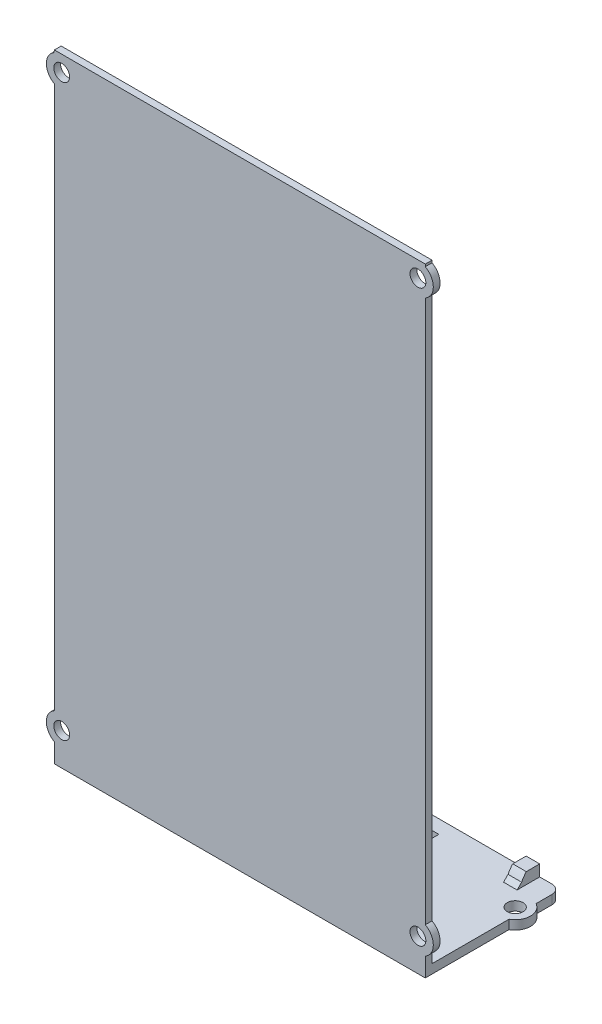
SolidWorks part; units mm, degrees
ref_plane "Front Plane" through (0, 0, 0) normal (0, 0, 1) x (1, 0, 0)
ref_plane "Top Plane" through (0, 0, 0) normal (0, 1, 0) x (1, 0, 0)
ref_plane "Right Plane" through (0, 0, 0) normal (1, 0, 0) x (0, 0, -1)
sketch "Sketch1" plane through (0, 0, 0) normal (0, 0, 1) x (1, 0, 0)
  line L0 (-37.75, -134.5) -> (37.75, -134.5)
  line L1 (-41, -126.5135) -> (-41, -6.4865) construction
  line L2 (-37.75, -132.4865) -> (-37.75, -134.5) construction
  line L3 (41, 0) -> (-41, 0) construction
  line L4 (41, -0.5135) -> (41, 0) construction
  line L5 (-37.75, -7) -> (-37.75, -126.5135) construction
  line L6 (37.75, -7) -> (-37.75, -7) construction
  line L28 (-41, -6.4865) -> (-41, -126.5135)
  line L29 (-41, -132.4865) -> (-41, -134.5)
  line L30 (-41, -134.5) -> (-37.75, -134.5)
  line L31 (-37.75, -134.5) -> (-37.75, -132.4865) construction
  line L32 (-37.75, -126.5135) -> (-37.75, -7) construction
  line L33 (-37.75, -7) -> (37.75, -7) construction
  line L34 (37.75, -7) -> (37.75, -126.5135) construction
  line L35 (37.75, -132.4865) -> (37.75, -134.5) construction
  line L36 (37.75, -134.5) -> (41, -134.5)
  line L37 (41, -134.5) -> (41, -132.4865)
  line L38 (41, -126.5135) -> (41, -6.4865)
  line L39 (41, -0.5135) -> (41, 0)
  line L40 (41, 0) -> (-41, 0)
  line L41 (-41, 0) -> (-41.0728, -0.5543)
  circle A0 centre (-39.375, -129.5) radius 1.75
  circle A1 centre (39.375, -129.5) radius 1.75
  circle A2 centre (39.375, -3.5) radius 1.75
  circle A3 centre (-39.375, -3.5) radius 1.75
  arc A4 (-37.75, -132.4865) -> (-37.75, -126.5135) centre (-39.375, -129.5) ccw construction
  arc A5 (41, -6.4865) -> (41, -0.5135) centre (39.375, -3.5) ccw construction
  arc A12 (-41, -126.5135) -> (-41, -132.4865) centre (-39.375, -129.5) ccw
  arc A13 (-37.75, -132.4865) -> (-37.75, -126.5135) centre (-39.375, -129.5) ccw construction
  arc A14 (37.75, -126.5135) -> (37.75, -132.4865) centre (39.375, -129.5) ccw construction
  arc A15 (41, -132.4865) -> (41, -126.5135) centre (39.375, -129.5) ccw
  arc A16 (41, -6.4865) -> (41, -0.5135) centre (39.375, -3.5) ccw
  arc A17 (-41.0728, -0.5543) -> (-41, -6.4865) centre (-39.375, -3.5) ccw
  dimension "D2" = 3.5
extrude "Boss-Extrude1" add sketch "Sketch1" along normal blind 1.5
sketch "Sketch2" plane through (-41, 0, 0) normal (-1, 0, 0) x (0, 0, 1)
  line L0 (1.5, -134.5) -> (1.5, -136.7)
  line L1 (1.5, -136.7) -> (-40, -136.7)
  line L2 (-40, -136.7) -> (-40, -134.7)
  line L3 (-40, -134.7) -> (0, -134.7)
  line L4 (0, -134.7) -> (0, -134.5)
  line L10 (0, -132.4865) -> (0, -134.5)
  line L11 (0, -134.5) -> (1.5, -134.5)
  line L12 (1.5, -134.5) -> (1.5, -132.4865)
  line L13 (1.5, -132.4865) -> (0, -132.4865)
  line L14 (0, -132.4865) -> (0, -134.5)
  line L16 (1.5, -134.5) -> (1.5, -132.4865)
  line L17 (1.5, -132.4865) -> (0, -132.4865)
  dimension "D1" = 2
  dimension "D2" = 0.2
  dimension "D4" = 40
  dimension "D3" = 0
extrude "Boss-Extrude2" add sketch "Sketch2" against normal up to surface (82 mm away) up to face at (41, -133.4933, 0.75)
sketch "Sketch3" plane through (-15, 0, 0) normal (1, 0, 0) x (0, 0, -1)
  line L0 (0, -119.7) -> (15, -134.7)
  line L1 (0, -126.5135) -> (0, -6.4865) construction
  line L2 (40, -134.7) -> (0, -134.7) construction
  line L3 (15, -134.7) -> (0, -134.7)
  line L4 (0, -134.7) -> (0, -119.7)
  dimension "D1" = 15
extrude "Boss-Extrude3" add sketch "Sketch3" along normal blind 1.5 and the other way blind 1.5
sketch "Sketch4" plane through (0, -136.7, 0) normal (0, -1, 0) x (1, 0, 0)
  line L0 (-41, -17.0135) -> (-41, -22.9865)
  line L1 (41, -17.0135) -> (41, -22.9865)
  line L9 (-41, -40) -> (-41, 1.5) construction
  line L10 (41, 1.5) -> (41, -40) construction
  line L11 (41, -17.0135) -> (39.375, -20) construction
  line L12 (39.375, -20) -> (41, -22.9865) construction
  arc A2 (-41, -17.0135) -> (-41, -22.9865) centre (-39.375, -20) ccw
  arc A3 (41, -22.9865) -> (41, -17.0135) centre (39.375, -20) ccw
  arc A4 (-41, -17.0135) -> (-41, -22.9865) centre (-39.375, -20) ccw construction
  arc A5 (41, -22.9865) -> (41, -17.0135) centre (39.375, -20) ccw construction
extrude "Boss-Extrude4" add sketch "Sketch4" against normal blind 2
sketch "Sketch5" plane through (0, -136.7, 0) normal (0, -1, 0) x (1, 0, 0)
  arc A0 (41, -22.9865) -> (41, -17.0135) centre (39.375, -20) ccw construction
  circle A1 centre (39.375, -20) radius 1.75
  circle A6 centre (-39.375, -20) radius 1.75
  arc A7 (-41, -17.0135) -> (-41, -22.9865) centre (-39.375, -20) ccw construction
  dimension "D1" = 3.5
  dimension "D2" = 3.5
extrude "Cut-Extrude1" cut sketch "Sketch5" against normal blind 2
sketch "Sketch6" plane through (0, -136.7, 0) normal (0, -1, 0) x (1, 0, 0)
  line L0 (-57.6714, -28.5) -> (65.3337, -28.5)
extrude "Cut-Extrude2" cut sketch "Sketch6" against normal through all and the other way through all
sketch "Sketch7" plane through (0, -136.7, 0) normal (0, -1, 0) x (1, 0, 0)
  line L0 (-41, -28.5) -> (41, -28.5) construction
  line L1 (-36.3, -28.5) -> (-33.3, -28.5)
  line L2 (-36.3, -28.5) -> (-36.3, -24.5)
  line L3 (-36.3, -24.5) -> (-33.3, -24.5)
  line L4 (-33.3, -28.5) -> (-33.3, -24.5)
  line L5 (-41, -25.7433) -> (-36.3, -25.7433) construction
  line L6 (36.3, -28.5) -> (33.3, -28.5)
  line L7 (36.3, -28.5) -> (36.3, -24.5)
  line L8 (36.3, -24.5) -> (33.3, -24.5)
  line L9 (33.3, -28.5) -> (33.3, -24.5)
  line L10 (-41, -28.5) -> (-41, -22.9865) construction
  line L11 (36.3, -24.5) -> (41, -24.5) construction
  line L12 (41, -22.9865) -> (41, -28.5) construction
  dimension "D1" = 4.7
  dimension "D2" = 3
  dimension "D3" = 4
extrude "Boss-Extrude6" add sketch "Sketch7" against normal blind 2.5 from surface at -2 starting at face at (-39.375, -134.7, -21.75)
fillet "Fillet1" radius 2 2 edges at (-41, -135.7, -28.5) (41, -135.7, -28.5)
chamfer "Chamfer1" distance 1 angle 45 4 edges at (-34.8, -132.2, -24.5) (34.8, -132.2, -24.5) (-34.8, -134.7, -24.5) (34.8, -134.7, -24.5)
fillet "Fillet2" radius 8 2 edges at (-34.8, -133.2, -24.5) (34.8, -133.2, -24.5)
sketch "Sketch8" plane through (0, -136.7, 0) normal (0, -1, 0) x (1, 0, 0)
  line L0 (-41, -17.0135) -> (-41, 1.5) construction
  line L1 (-9, -2.5) -> (17, -2.5)
  line L2 (-9, -2.5) -> (-9, -25.5)
  line L3 (-9, -25.5) -> (17, -25.5)
  line L4 (17, -2.5) -> (17, -25.5)
  line L5 (41, 1.5) -> (-41, 1.5) construction
  line L6 (-39, -28.5) -> (39, -28.5) construction
  dimension "D1" = 32
  dimension "D2" = 58
  dimension "D3" = 4
  dimension "D4" = 3
extrude "Cut-Extrude3" cut sketch "Sketch8" against normal blind 22.4262
